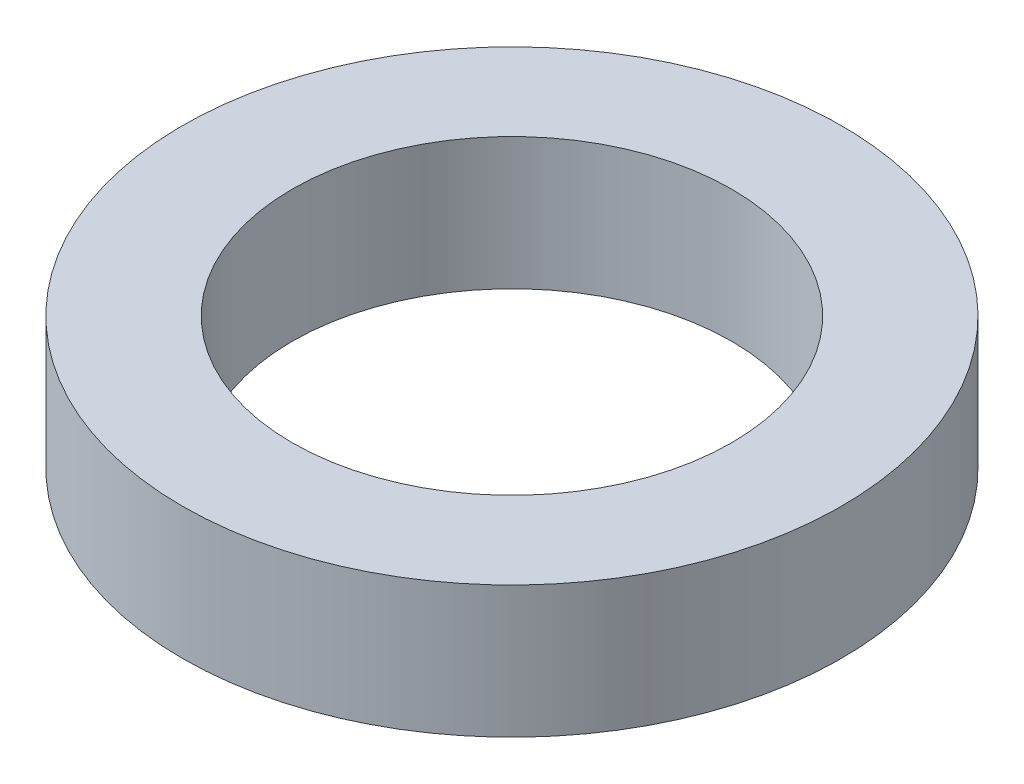
SolidWorks part; units mm, degrees
ref_plane "Front Plane" through (0, 0, 0) normal (0, 0, 1) x (1, 0, 0)
ref_plane "Top Plane" through (0, 0, 0) normal (0, 1, 0) x (1, 0, 0)
ref_plane "Right Plane" through (0, 0, 0) normal (1, 0, 0) x (0, 0, -1)
sketch "Sketch1" plane through (0, 0, 0) normal (0, 1, 0) x (1, 0, 0)
  circle A0 centre (0, 0) radius 75
  dimension "FLANGE_OD" = 150
extrude "Boss-Extrude1" add sketch "Sketch1" along normal blind 30
sketch "Sketch2" plane through (0, 0, 0) normal (0, 1, 0) x (1, 0, 0)
  circle A0 centre (0, 0) radius 50
  dimension "BORE_D" = 100
extrude "Cut-Extrude1" cut sketch "Sketch2" along normal through all
sketch "Sketch3" plane through (0, 30, 0) normal (0, 1, 0) x (1, 0, 0)
  circle A0 centre (0, 0) radius 30.5973 construction
  circle A1 centre (-30.5973, 0) radius 2.7354
  dimension "BOLT_D" = 5.4707
  dimension "BOLT_PCD" = 61.1946
extrude "Cut-Extrude2" cut sketch "Sketch3" against normal blind 24.02 rebuild error yes
pattern_circular "CirPattern1" count 8 over 360 rebuild error yes
